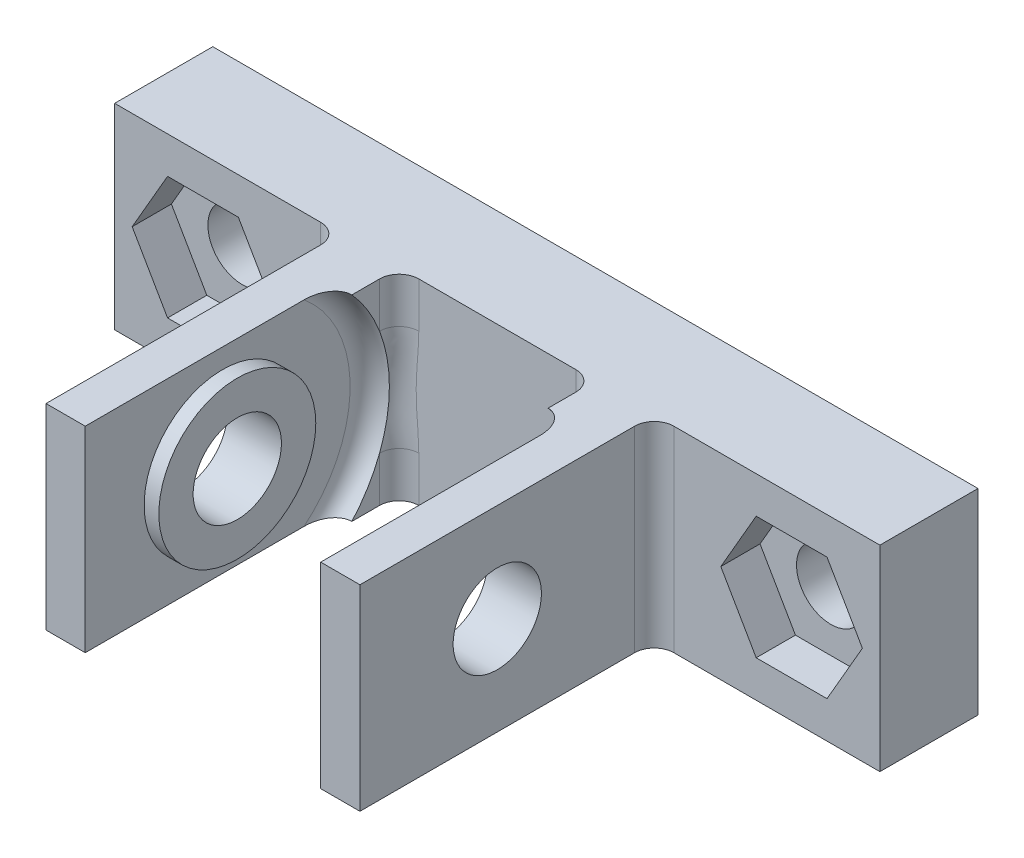
SolidWorks part; units mm, degrees
ref_plane "Front Plane" through (0, 0, 0) normal (0, 0, 1) x (1, 0, 0)
ref_plane "Top Plane" through (0, 0, 0) normal (0, 1, 0) x (1, 0, 0)
ref_plane "Right Plane" through (0, 0, 0) normal (1, 0, 0) x (0, 0, -1)
sketch "Sketch1" plane through (0, 0, 0) normal (0, 1, 0) x (1, 0, 0)
  line L0 (0, 0) -> (0, -20.0709) construction
  line L1 (-8, 0) -> (8, 0)
  line L2 (8, 0) -> (8, -20)
  line L3 (8, -20) -> (5, -20)
  line L4 (5, -20) -> (5, -5)
  line L5 (5, -5) -> (-5, -5)
  line L6 (-5, -20) -> (-5, -5)
  line L7 (-8, -20) -> (-5, -20)
  line L8 (-8, 0) -> (-8, -20)
  line L9 (5, -20) -> (5, -5)
  point P9 (0, -5)
  dimension "D1" = 5
  dimension "D2" = 3
  dimension "D3" = 15
  dimension "D4" = 5
extrude "Boss-Extrude1" add sketch "Sketch1" along normal blind 10 contours L1 L0 L5 L4 L3 L2 | L0 L1 L8 L7 L6 L5 region at (5.3235, 0, 7.7941) region at (-5.3235, 0, 7.7941)
sketch "Sketch2" plane through (8, 0, 0) normal (1, 0, 0) x (0, 0, -1)
  line L0 (-20, 5) -> (0, 5) construction
  line L1 (-20, 10) -> (-20, 0) construction
  line L2 (0, 10) -> (0, 0) construction
  circle A0 centre (-13, 5) radius 2.25
  dimension "D1" = 4.5
  dimension "D2" = 13
extrude "Cut-Extrude1" cut sketch "Sketch2" against normal through all contours A0
sketch "Sketch3" plane through (0, 10, 0) normal (0, 1, 0) x (1, 0, 0)
  line L1 (-19.5, -5) -> (19.5, -5)
  line L2 (0, 0) -> (0, -5) construction
  line L3 (-19.5, 0) -> (19.5, 0)
  line L4 (19.5, -5) -> (19.5, 0)
  line L5 (-8, 0) -> (8, 0) construction
  line L7 (-19.5, -5) -> (-19.5, 0)
  line L8 (5, -5) -> (-5, -5) construction
  dimension "D1" = 19.5
extrude "Boss-Extrude2" add sketch "Sketch3" against normal through all
sketch "Sketch4" plane through (0, 0, 5) normal (0, 0, 1) x (1, 0, 0)
  line L0 (-19.5, 5) -> (-8, 5) construction
  line L1 (-19.5, 0) -> (-19.5, 10) construction
  line L2 (-8, 10) -> (-8, 0) construction
  line L3 (-15, 0) -> (-15, 10) construction
  line L6 (0, 0) -> (0, 10) construction
  line L7 (5, 0) -> (-5, 0) construction
  line L8 (5, 10) -> (-5, 10) construction
  line L9 (15, 0) -> (15, 10) construction
  line L10 (19.5, 5) -> (8, 5) construction
  line L11 (-15, 0) -> (-15, 10) construction
  circle A0 centre (-15, 5) radius 1.75
  circle A1 centre (15, 5) radius 1.75
  dimension "D1" = 3.5
  dimension "D2" = 15
extrude "Cut-Extrude2" cut sketch "Sketch4" against normal through all
sketch "Sketch6" plane through (-5, 0, 0) normal (1, 0, 0) x (0, 0, -1)
  line L0 (-13, 12.5) -> (-20.5, 12.5)
  line L1 (-20.5, 12.5) -> (-20.5, 5)
  line L2 (-20.5, 5) -> (-20.5, -2.5)
  line L3 (-20.5, -2.5) -> (-13, -2.5)
  arc A0 (-13, -2.5) -> (-13, 12.5) centre (-13, 5) ccw
  circle A1 centre (-13, 5) radius 2.25 construction
  dimension "D1" = 15
extrude "Cut-Extrude3" cut sketch "Sketch6" against normal blind 1
sketch "Sketch5" plane through (-6, 0, 0) normal (1, 0, 0) x (0, 0, -1)
  circle A0 centre (-13, 5) radius 4
  circle A1 centre (-13, 5) radius 2.25
  circle A2 centre (-13, 5) radius 2.25 construction
  dimension "D1" = 8
extrude "Boss-Extrude3" add sketch "Sketch5" along normal blind 0.75
mirror "Mirror1" about plane through (0, 0, 0) normal (1, 0, 0) of "Boss-Extrude3", "Cut-Extrude3"
fillet "Fillet1" radius 1 6 edges at (-6, 5, 5.5) (6, 5, 5.5) (5, 5, 5) (-5, 5, 5) (8, 5, 5) (-8, 5, 5)
sketch "Sketch7" plane through (0, 0, 5) normal (0, 0, 1) x (1, 0, 0)
  line L0 (0, 10) -> (0, 0) construction
  line L1 (16.8042, 8.125) -> (13.1958, 8.125)
  line L2 (13.1958, 8.125) -> (11.3916, 5)
  line L3 (11.3916, 5) -> (13.1958, 1.875)
  line L4 (13.1958, 1.875) -> (16.8042, 1.875)
  line L5 (16.8042, 1.875) -> (18.6084, 5)
  line L6 (18.6084, 5) -> (16.8042, 8.125)
  line L7 (4, 10) -> (-4, 10) construction
  line L8 (-18.6084, 5) -> (-16.8042, 8.125)
  line L9 (-16.8042, 1.875) -> (-18.6084, 5)
  line L10 (-13.1958, 1.875) -> (-16.8042, 1.875)
  line L11 (-11.3916, 5) -> (-13.1958, 1.875)
  line L12 (-13.1958, 8.125) -> (-11.3916, 5)
  line L13 (-16.8042, 8.125) -> (-13.1958, 8.125)
  line L14 (18.6084, 5) -> (16.8042, 8.125)
  circle A0 centre (15, 5) radius 3.125 construction
  circle A1 centre (-15, 5) radius 3.125 construction
  circle M5 centre (15, 5) radius 1.75
  dimension "D1" = 6.25
extrude "Cut-Extrude4" cut sketch "Sketch7" against normal blind 2 contours L13 L8 L9 L10 L11 L12 | L5 L6 L1 L2 L3 L4 M5 | M5 region at (17.6236, 6.5148, 5) region at (-15, 5, 5) region at (15, 5, 5)
equation "\"X-ROD-SPACING\"=45"
equation "\"Y-ROD-SPACING\"=75"
equation "\"Z-ROD-SPACING\"=17.5"
equation "\"Y-BED-OFFSET\"=2"
equation "\"Y-BED-ROD-INSET\"=3.5"
equation "\"Y-BED-SCREW-SPACING\"=209"
equation "\"Y-BED-SCREW-CUTOUT-SLOT-HEIGHT\"=2"
equation "\"T-SLOT-NUT-FILLET-RADIUS\"=0.5"
equation "\"T-SLOT-SCREW-SHAFT-RADIUS\"=1.55"
equation "\"T-SLOT-SCREW-SHAFT-CUTOUT-LENGTH\"=11"
equation "\"T-SLOT-NUT-DEPTH\"=3.5"
equation "\"T-SLOT-NUT-WIDTH\"=2.85"
equation "\"T-SLOT-NUT-END-DISTANCE\"=8"
equation "\"ACRYLIC-THICKNESS\"=10"
equation "\"ACRYLIC-THICKNESS2\"=4.5"
equation "\"ACRYLIC-TAB-CUTOUT-SIZE\"=\"ACRYLIC-THICKNESS\"+\"ACRYLIC-TAB-TOLERANCE\"*2"
equation "\"ACRYLIC-TAB-TOLERANCE\"=-.05"
equation "\"KERF\"=0.1"
equation "\"ACRYLIC-THICKNESS-TAB-CUTOUT-WIDTH\"=\"ACRYLIC-THICKNESS\"-\"KERF\"*2"
equation "\"ACRYLIC-THICKNESS-TAB-CUTOUT-HEIGHT\"=\"ACRYLIC-TAB-WIDTH\"-\"KERF\"*4"
equation "\"ACRYLIC-THICKNESS2-TAB-CUTOUT-WIDTH\"=\"ACRYLIC-THICKNESS2\"-\"KERF\"*2"
equation "\"ACRYLIC-THICKNESS2-TAB-CUTOUT-HEIGHT\"=\"ACRYLIC-TAB-WIDTH\"-\"KERF\"*4"
equation "\"ACRYLIC-TAB-WIDTH\"=\"ACRYLIC-THICKNESS\""
equation "\"ACRYLIC-M3-HOLE\"=2.9"
equation "\"SMOOTHROD-CAP-SCREW-DISTANCE\"=20"
equation "\"FRAME-WIDTH-INNER\"=370"
equation "\"NEMA17-HOLE-SPACING\"=31"
equation "\"NEMA17-CENTRAL-CUTOUT\"=22.5"
equation "\"Z-BRACKET-REACH\"=55"
equation "\"Z-ROD-INSET\"=13.5"
equation "\"TOP-BRACKET-SPACING\"=40"
equation "\"SMOOTHROD-X-LENGTH\"=350"
equation "\"SMOOTHROD-Y-LENGTH\"=350"
equation "\"SMOOTHROD-Z-LENGTH\"=350"
equation "\"SMOOTHROD-TIGHTENING-HEADROOM\"=.25"
equation "\"LEADSCREW-Z-LENGTH\"=300"
equation "\"SCREW-LENGTH-FRAME\"=\"ACRYLIC-THICKNESS\" + 10"
equation "\"SCREW-LENGTH-MOTOR\"=\"ACRYLIC-THICKNESS\" + 5"
equation "\"SCREW-LENGTH-EXTRUDER\"=28"
equation "\"SCREW-HEAD-RADIUS\"=6"
equation "\"PRINTED-M3-HOLE\"=3.5"
equation "\"PRINTED-X-SMOOTHROD-DIAMETER\"=9.0"
equation "\"PRINTED-X-SMOOTHROD-CUTOUT\"=10"
equation "\"PRINTED-X-BASE-HEIGHT\"=10"
equation "\"PRINTED-LM8UU-CUTOUT-SIZE\"=15.5"
equation "\"PRINTED-LM8UU-CUTOUT-LENGTH\"=24.5"
equation "\"PRINTED-X-IDLER-HEIGHT\"=16"
equation "\"PRINTED-M3-NUT-AF\"=6.25"
equation "\"PSU-MOUNTING-WIDTH\"=95"
equation "\"PSU-MOUNTING-HEIGHT\"=177"
equation "\"Y-BELT-TO-ROD-DISTANCE\"=20"
equation "\"SPOOL-HOLDER-ROD-SPACING\"=150"
equation "\"ACRYLIC-X-CARRIAGE-WIDTH\"=55"
equation "\"ACRYLIC-X-CARRIAGE-HEIGHT\"=75"
equation "\"ACRYLIC-X-CARRIAGE-LM8UU-CUTOUT-WIDTH\"=24.25"
equation "\"ACRYLIC-X-CARRIAGE-LM8UU-CUTOUT-HEIGHT\"=11.0"
equation "\"ACRYLIC-X-CARRIAGE-SCREW-SPACING-X\"=15"
equation "\"ACRYLIC-X-CARRIAGE-SCREW-SPACING-Y\"=33"
equation "\"ACRYLIC-X-CARRIAGE-CENTER-TAB-SPACING\"=14"
equation "\"ACRYLIC-X-CARRIAGE-EXTRUDER-OFFSET\"=26"
equation "\"ACRYLIC-X-CARRIAGE-EXTRUDER-ANGLE\"=90"
equation "\"ACRYLIC-X-CARRIAGE-EXTRUDER-SHELF-DEPTH\"=\"ACRYLIC-X-CARRIAGE-EXTRUDER-OFFSET\" + 28"
equation "\"ACRYLIC-X-CARRIAGE-EXTRUDER-BRACE-SPACING\"=23"
equation "\"ACRYLIC-X-CARRIAGE-EXTRUDER-BRACE-TAB-OFFSET\"=20"
equation "\"ACRYLIC-X-CARRIAGE-EXTRUDER-BRACE-HEIGHT\"=35"
equation "\"ACRYLIC-X-CARRIAGE-EXTRUDER-BRACE-SCREW-SPACING\"=22"
equation "\"ACRYLIC-X-CARRIAGE-DUAL-WIDTH-MULTIPLIER\"=1.65"
equation "\"ACRYLIC-X-CARRIAGE-DUAL-HOTEND-SPACING\"=42"
equation "\"ACRYLIC-X-CARRIAGE-DUAL-WIDTH\"=75"
equation "\"ACRYLIC-X-CARRIAGE-DUAL-FAN-OFFSET\"=52"
equation "\"ACRYLIC-X-CARRIAGE-DUAL-FAN-HEIGHT\"=20"
equation "\"ACRYLIC-X-CARRIAGE-DUAL-HOTEND-SEPARATION\"=36"
equation "\"ACRYLIC-X-CARRIAGE-DUAL-MOUNT-PLATE-DEPTH\"=75"
equation "\"ACRYLIC-X-CARRIAGE-DUAL-MOUNT-BRACE-WIDTH\"=33"
equation "\"ACRYLIC-X-CARRIAGE-DUAL-MOUNT-SCREW-WIDTH\"=40"
equation "\"BLOWER-FAN-WIDTH\"=15"
equation "\"D1@Sketch7\"=\"PRINTED-M3-NUT-AF\""
